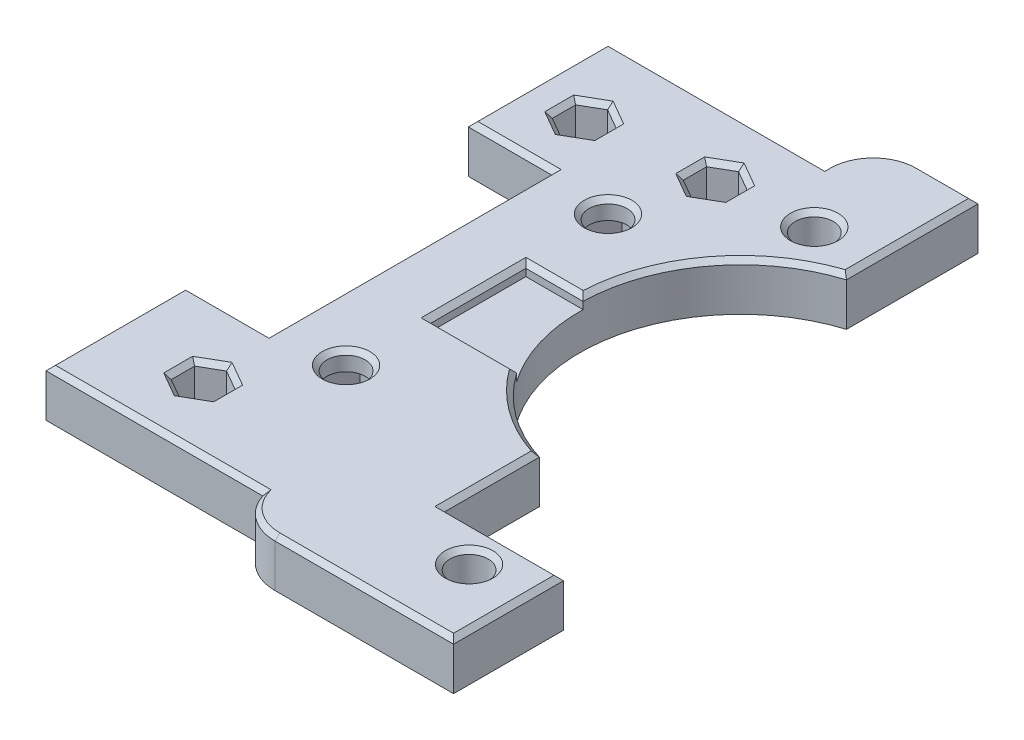
SolidWorks part; units mm, degrees
ref_plane "前视基准面" through (0, 0, 0) normal (0, 0, 1) x (1, 0, 0)
ref_plane "上视基准面" through (0, 0, 0) normal (0, 1, 0) x (1, 0, 0)
ref_plane "右视基准面" through (0, 0, 0) normal (1, 0, 0) x (0, 0, -1)
other "Configuration Table"
sketch "草图1" plane through (0, 0, 0) normal (0, 1, 0) x (1, 0, 0)
  line L1 (0, 0) -> (20, 0)
  line L2 (0, 0) -> (0, 35.74)
  line L3 (0, 35.74) -> (20, 35.74)
  line L4 (20, 0) -> (20, 35.74)
  dimension "D1" = 35.74
  dimension "D2" = 20
extrude "凸台-拉伸1" add sketch "草图1" along normal blind 4
sketch "草图2" plane through (0, 0, 0) normal (0, -1, 0) x (1, 0, 0)
  line L0 (20, 0) -> (20, -35.74) construction
  line L1 (20, 0) -> (11.2, 0)
  line L2 (20, 0) -> (20, 8.5)
  line L3 (20, 8.5) -> (11.2, 8.5)
  line L4 (11.2, 0) -> (11.2, 8.5)
  line L5 (20, -35.74) -> (0, -35.74) construction
  line L6 (20, -35.74) -> (11.2, -35.74)
  line L7 (20, -35.74) -> (20, -45.54)
  line L8 (20, -45.54) -> (11.2, -45.54)
  line L9 (11.2, -35.74) -> (11.2, -45.54)
  line L10 (0, 0) -> (20, 0) construction
  dimension "D1" = 8.8
  dimension "D2" = 8.8
  dimension "D3" = 8.5
  dimension "D4" = 0
  dimension "D5" = 9.8
extrude "凸台-拉伸2" add sketch "草图2" against normal blind 4
sketch "草图3" plane through (0, 0, 0) normal (0, -1, 0) x (-1, 0, 0)
  line L0 (-20, -8.5) -> (-11.2, -8.5) construction
  line L1 (-20, -8.5) -> (-20, 45.54) construction
  circle A0 centre (-24, 21.6) radius 13.5
  dimension "D3" = 27
  dimension "D1" = 30.1
  dimension "D2" = 4
extrude "切除-拉伸1" cut sketch "草图3" against normal blind 10
sketch "草图4" plane through (0, 0, 0) normal (0, -1, 0) x (-1, 0, 0)
  line L1 (-18, 1.75) -> (-9, 1.75)
  line L2 (-18, 1.75) -> (-18, -3.25)
  line L3 (-18, -3.25) -> (-9, -3.25)
  line L4 (-9, 1.75) -> (-9, -3.25)
  line L7 (-20, -8.5) -> (-11.2, -8.5) construction
  line L8 (-20, -8.5) -> (-20, 8.7062) construction
  dimension "D1" = 5
  dimension "D2" = 9
  dimension "D3" = 5.25
  dimension "D4" = 2
extrude "切除-拉伸2" cut sketch "草图4" against normal blind 1
sketch "草图5" plane through (20, 0, 0) normal (1, 0, 0) x (0, 0, -1)
  line L0 (-8.5, 4) -> (-8.5, 0) construction
  line L1 (-8.5, 0) -> (0.729, 0)
  line L2 (-8.5, 0) -> (-8.5, 4)
  line L3 (-8.5, 4) -> (0.729, 4)
  line L4 (0.729, 0) -> (0.729, 4)
  line L5 (-8.5, 0) -> (8.7062, 0) construction
  line L6 (-8.5, 4) -> (8.7062, 4) construction
extrude "凸台-拉伸3" add sketch "草图5" along normal blind 10
sketch "草图6" plane through (0, 0, 0) normal (0, -1, 0) x (-1, 0, 0)
  line L0 (-11.2, 35.74) -> (-11.2, 45.54) construction
  line L1 (-11.2, 45.54) -> (-20, 45.54) construction
  line L2 (-30, -8.5) -> (-11.2, -8.5) construction
  line L3 (-11.2, -8.5) -> (-11.2, -3.25) construction
  circle A0 centre (-15.2, 36.59) radius 1.6
  circle A1 centre (-25.25, -2.45) radius 1.6
  dimension "D1" = 4
  dimension "D2" = 8.95
  dimension "D3" = 3.2
  dimension "D4" = 6.05
  dimension "D5" = 14.05
  dimension "D6" = 3.2
extrude "切除-拉伸3" cut sketch "草图6" against normal blind 10
sketch "草图7" plane through (0, 0, 0) normal (0, -1, 0) x (-1, 0, 0)
  line L0 (0, 35.74) -> (0, 0) construction
  line L1 (-11.2, 35.74) -> (0, 35.74) construction
  circle A0 centre (-5.6, 28.87) radius 1.6
  circle A1 centre (-5.6, 6.87) radius 1.6
  point P6 (0, 17.87)
  point P9 (-5.6, 35.74)
  dimension "D1" = 3.2
  dimension "D2" = 3.2
  dimension "D3" = 11
  dimension "D4" = 11
  dimension "D5" = 0
  dimension "D6" = 0
extrude "切除-拉伸4" cut sketch "草图7" against normal through all
sketch "草图8" plane through (0, 0, 0) normal (0, -1, 0) x (1, 0, 0)
  line L0 (11.2, -35.74) -> (11.2, -45.54) construction
  line L1 (0, -35.74) -> (11.2, -35.74)
  line L2 (0, -35.74) -> (0, -39.74)
  line L3 (0, -39.74) -> (11.2, -39.74)
  line L4 (11.2, -35.74) -> (11.2, -39.74)
  line L5 (11.2, 8.5) -> (11.2, 3.25) construction
  line L6 (0, 0) -> (11.2, 0)
  line L7 (0, 0) -> (0, 4)
  line L8 (0, 4) -> (11.2, 4)
  line L9 (11.2, 0) -> (11.2, 4)
  dimension "D1" = 4
  dimension "D2" = 4
extrude "凸台-拉伸4" add sketch "草图8" against normal up to surface (4 mm away) up to face at (5.6, 4, -30.47)
sketch "草图9" plane through (0, 0, 0) normal (0, -1, 0) x (-1, 0, 0)
  circle A0 centre (-7.6, 35.87) radius 1.65
  circle A1 centre (-0.6, -0.13) radius 1.65
  circle A2 centre (-5.6, 6.87) radius 1.6 construction
  circle A3 centre (-5.6, 28.87) radius 1.6 construction
  dimension "D1" = 3.3
  dimension "D2" = 3.3
  dimension "D3" = 7
  dimension "D4" = 7
  dimension "D5" = 2
  dimension "D6" = 5
extrude "切除-拉伸5" cut sketch "草图9" against normal through all
sketch "草图10" plane through (0, 0, 0) normal (-1, 0, 0) x (0, 0, 1)
  line L0 (-39.74, 0) -> (-45.54, 0) construction
  line L1 (-39.74, 0) -> (-29.74, 0)
  line L2 (-39.74, 0) -> (-39.74, 4)
  line L3 (-39.74, 4) -> (-29.74, 4)
  line L4 (-29.74, 0) -> (-29.74, 4)
  line L5 (-39.74, 4) -> (-39.74, 0) construction
  line L6 (-39.74, 4) -> (-1.407, 4) construction
  line L7 (-39.74, 0) -> (-1.407, 0) construction
  line L8 (4, 4) -> (-6, 4)
  line L9 (4, 4) -> (4, 0)
  line L10 (4, 0) -> (-6, 0)
  line L11 (-6, 4) -> (-6, 0)
  dimension "D1" = 10
  dimension "D2" = 10
extrude "凸台-拉伸5" add sketch "草图10" along normal blind 7
sketch "草图11" plane through (0, 0, 0) normal (0, -1, 0) x (-1, 0, 0)
  circle A0 centre (2.4, 34.87) radius 1.65
  circle A1 centre (-7.6, 35.87) radius 1.65 construction
  dimension "D1" = 3.3
  dimension "D2" = 10
  dimension "D3" = 1
extrude "切除-拉伸6" cut sketch "草图11" against normal blind 8
sketch "草图12" plane through (0, 0, 0) normal (0, -1, 0) x (-1, 0, 0)
  line L1 (-11.2, -3.25) -> (-4.6, -3.25)
  line L2 (-11.2, -3.25) -> (-11.2, 1.75)
  line L3 (-11.2, 1.75) -> (-4.6, 1.75)
  line L4 (-4.6, -3.25) -> (-4.6, 1.75)
  dimension "D1" = 6.6
extrude "切除-拉伸7" cut sketch "草图12" against normal up to surface (1 mm away) up to face at (12.7333, 1, 0.5)
sketch "草图13" plane through (0, 0, 0) normal (0, -1, 0) x (-1, 0, 0)
  circle A0 centre (-0.6, -0.13) radius 1.55
extrude "切除-拉伸8" cut sketch "草图13" against normal blind 5
sketch "草图14" plane through (0, 0, 0) normal (0, -1, 0) x (-1, 0, 0)
  line L0 (-11.2, -8.5) -> (-11.2, -4) construction
  line L1 (7, -4) -> (-11.2, -4)
  line L2 (7, -4) -> (7, -5.73)
  line L3 (7, -5.73) -> (-11.2, -5.73)
  line L4 (-11.2, -4) -> (-11.2, -5.73)
  line L5 (-11.2, 39.74) -> (-11.2, 45.54) construction
  line L6 (7, 39.74) -> (-11.2, 39.74)
  line L7 (7, 39.74) -> (7, 41.47)
  line L8 (7, 41.47) -> (-11.2, 41.47)
  line L9 (-11.2, 39.74) -> (-11.2, 41.47)
  dimension "D1" = 1.73
  dimension "D2" = 1.73
extrude "凸台-拉伸6" add sketch "草图14" against normal up to surface (4 mm away) up to face at (-2.4, 4, -36.52)
sketch "草图16" plane through (0, 4, 0) normal (0, 1, 0) x (1, 0, 0)
  line L0 (0, 29.74) -> (0, 6) construction
  line L1 (5.7, 13.87) -> (15.7, 13.87)
  line L2 (5.7, 13.87) -> (5.7, 21.87)
  line L3 (5.7, 21.87) -> (15.7, 21.87)
  line L4 (15.7, 13.87) -> (15.7, 21.87)
  point P4 (5.7, 17.87)
  point P7 (0, 17.87)
  dimension "D1" = 8
  dimension "D2" = 0
  dimension "D3" = 10
  dimension "D4" = 5.7
extrude "切除-拉伸9" cut sketch "草图16" against normal blind 1
sketch "草图17" plane through (0, 0, 0) normal (0, -1, 0) x (-1, 0, 0)
  line L1 (-8.8332, 28.87) -> (-7.2166, 26.07)
  line L2 (-7.2166, 26.07) -> (-3.9834, 26.07)
  line L3 (-3.9834, 26.07) -> (-2.3668, 28.87)
  line L4 (-2.3668, 28.87) -> (-3.9834, 31.67)
  line L5 (-3.9834, 31.67) -> (-7.2166, 31.67)
  line L6 (-7.2166, 31.67) -> (-8.8332, 28.87)
  line L7 (-8.8332, 6.87) -> (-7.2166, 4.07)
  line L8 (-7.2166, 4.07) -> (-3.9834, 4.07)
  line L9 (-3.9834, 4.07) -> (-2.3668, 6.87)
  line L10 (-2.3668, 6.87) -> (-3.9834, 9.67)
  line L11 (-3.9834, 9.67) -> (-7.2166, 9.67)
  line L12 (-7.2166, 9.67) -> (-8.8332, 6.87)
  circle A0 centre (-5.6, 28.87) radius 2.8 construction
  circle A1 centre (-5.6, 6.87) radius 2.8 construction
  dimension "D1" = 5.6
  dimension "D2" = 5.6
extrude "切除-拉伸10" cut sketch "草图17" against normal blind 2.4
fillet "圆角1" radius 4 2 edges at (11.2, 2, 8.5) (11.2, 2, -45.54)
sketch "草图19" plane through (0, 4, 0) normal (0, 1, 0) x (1, 0, 0)
  line L1 (0.6, -2.093) -> (2.3, -1.1115)
  line L2 (2.3, -1.1115) -> (2.3, 0.8515)
  line L3 (2.3, 0.8515) -> (0.6, 1.833)
  line L4 (0.6, 1.833) -> (-1.1, 0.8515)
  line L5 (-1.1, 0.8515) -> (-1.1, -1.1115)
  line L6 (-1.1, -1.1115) -> (0.6, -2.093)
  line L7 (-2.4, 32.907) -> (-0.7, 33.8885)
  line L8 (-0.7, 33.8885) -> (-0.7, 35.8515)
  line L9 (-0.7, 35.8515) -> (-2.4, 36.833)
  line L10 (-2.4, 36.833) -> (-4.1, 35.8515)
  line L11 (-4.1, 35.8515) -> (-4.1, 33.8885)
  line L12 (-4.1, 33.8885) -> (-2.4, 32.907)
  line L13 (7.6, 33.907) -> (9.3, 34.8885)
  line L14 (9.3, 34.8885) -> (9.3, 36.8515)
  line L15 (9.3, 36.8515) -> (7.6, 37.833)
  line L16 (7.6, 37.833) -> (5.9, 36.8515)
  line L17 (5.9, 36.8515) -> (5.9, 34.8885)
  line L18 (5.9, 34.8885) -> (7.6, 33.907)
  circle A0 centre (0.6, -0.13) radius 1.7 construction
  circle A1 centre (-2.4, 34.87) radius 1.7 construction
  circle A2 centre (7.6, 35.87) radius 1.7 construction
  dimension "D1" = 3.4
  dimension "D2" = 3.4
  dimension "D3" = 3.4
extrude "切除-拉伸11" cut sketch "草图19" against normal through all
chamfer "倒角1" distance 0.4 angle 45 43 edges at (25.25, 4, 0.85) (15.2, 4, -38.19) (5.6, 4, -8.47) (5.6, 4, -30.47) (-7, 4, -0.135) (-3.5, 4, -6) (0, 4, -17.87) (-3.5, 4, -29.74) (-7, 4, -35.605) (2.1, 4, -41.47) (11.2, 4, -41.505) (12.3716, 4, -44.3684) (17.6, 4, -45.54) (20, 4, -40.0169) (16.0359, 4, -10.6994) (13.2121, 4, -29.7161) (20, 4, -4.7176) (25, 4, -0.729) (30, 4, 3.8855) (22.5031, 4, 8.5) (12.6525, 4, 7.7342) (2.1, 4, 5.73) (8.1014, 4, -21.87) (5.7, 4, -17.87) (9.3161, 4, -13.87) (9.3, 4, -35.87) (8.45, 4, -37.3422) (6.75, 4, -37.3422) (5.9, 4, -35.87) (6.75, 4, -34.3978) (8.45, 4, -34.3978) (-0.7, 4, -34.87) (-1.55, 4, -36.3422) (-3.25, 4, -36.3422) (-4.1, 4, -34.87) (-3.25, 4, -33.3978) (-1.55, 4, -33.3978) (2.3, 4, 0.13) (1.45, 4, -1.3422) (-0.25, 4, -1.3422) (-1.1, 4, 0.13) (-0.25, 4, 1.6022) (1.45, 4, 1.6022)
